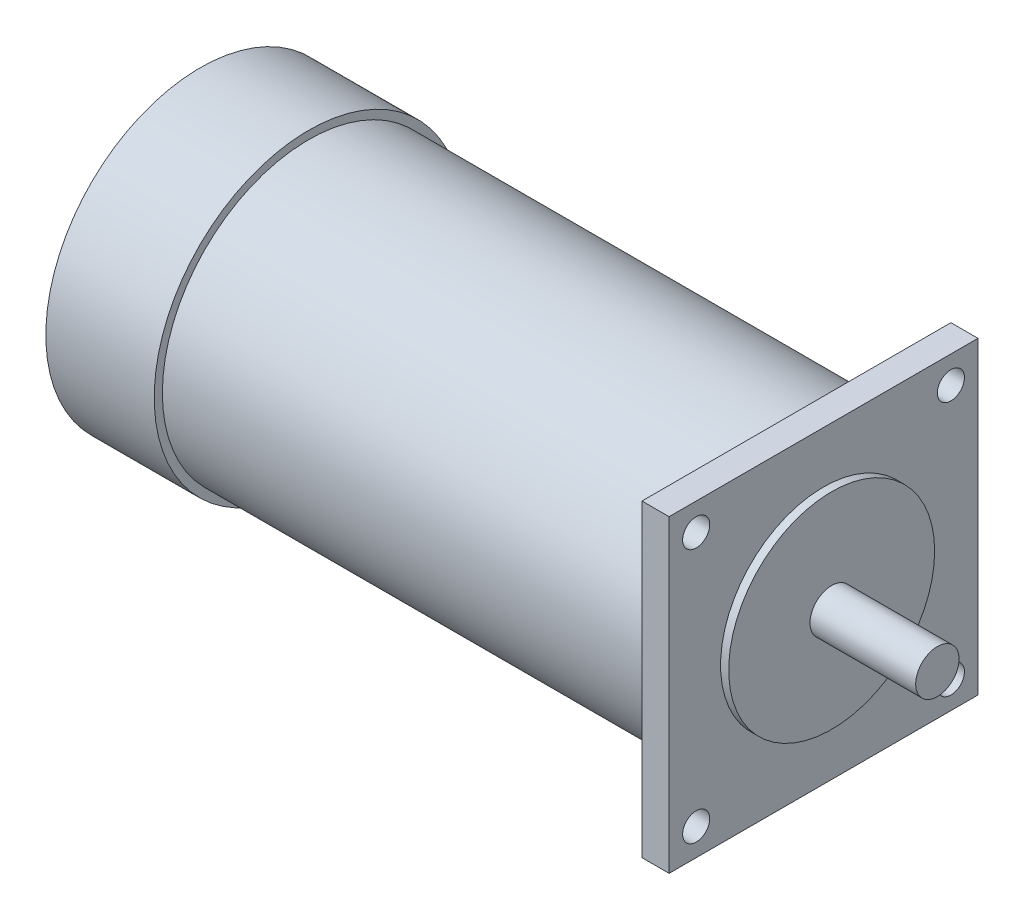
SolidWorks part; units mm, degrees
ref_plane "前视基准面" through (0, 0, 0) normal (0, 0, 1) x (1, 0, 0)
ref_plane "上视基准面" through (0, 0, 0) normal (0, 1, 0) x (1, 0, 0)
ref_plane "右视基准面" through (0, 0, 0) normal (1, 0, 0) x (0, 0, -1)
sketch "草图1" plane through (0, 0, 0) normal (1, 0, 0) x (0, 0, -1)
  line L1 (-28.5, -28.5) -> (28.5, -28.5)
  line L2 (-28.5, -28.5) -> (-28.5, 28.5)
  line L3 (-28.5, 28.5) -> (28.5, 28.5)
  line L4 (28.5, -28.5) -> (28.5, 28.5)
  line L5 (-28.5, -28.5) -> (28.5, 28.5) construction
  line L6 (-28.5, 28.5) -> (28.5, -28.5) construction
  circle A0 centre (0, 0) radius 19
  circle A1 centre (0, 0) radius 4
  point P0 (0, 0)
  dimension "D3" = 38
  dimension "D4" = 8
  dimension "D1" = 57
  dimension "D2" = 57
extrude "凸台-拉伸1" add sketch "草图1" along normal blind 21 contours A1 region at (0, 0, 0)
extrude "凸台-拉伸2" add sketch "草图1<3>" along normal blind 1.5 contours A0 A1 region at (0, 0, 18.4626)
sketch "草图1<3>" plane through (0, 0, 0) normal (1, 0, 0) x (0, 0, -1) same geometry as "草图1"
extrude "凸台-拉伸3" add sketch "草图1<4>" against normal blind 115 separate body contours L1 L4 L3 L2 A0 region at (0, 0, 27.6939)
sketch "草图1<4>" plane through (0, 0, 0) normal (1, 0, 0) x (0, 0, -1) same geometry as "草图1"
sketch "草图3" plane through (0, 0, 0) normal (1, 0, 0) x (0, 0, -1)
  line L4 (-28.5, -28.5) -> (28.5, -28.5)
  line L5 (28.5, -28.5) -> (28.5, 28.5)
  line L6 (28.5, 28.5) -> (-28.5, 28.5)
  line L7 (-28.5, 28.5) -> (-28.5, -28.5)
  line L8 (-28.5, -28.5) -> (28.5, -28.5)
  line L9 (28.5, -28.5) -> (28.5, 28.5)
  line L10 (28.5, 28.5) -> (-28.5, 28.5)
  line L11 (-28.5, 28.5) -> (-28.5, -28.5)
  line L16 (-28.5, 28.5) -> (0, 0) construction
  line L17 (0, 0) -> (28.5, -28.5) construction
  line L18 (-28.5, -28.5) -> (28.5, 28.5) construction
  circle A0 centre (-23.5, 23.5) radius 2.5
  circle A1 centre (23.5, 23.5) radius 2.5
  circle A2 centre (23.5, -23.5) radius 2.5
  circle A3 centre (-23.5, -23.5) radius 2.5
  point P17 (0, 0)
  dimension "D2" = 5
  dimension "D3" = 5
  dimension "D1" = 0
  dimension "D4" = 4
ref_plane "基准面2" through (21, 0, 0) normal (1, 0, 0) x (0, 0, -1)
sketch "草图5" plane through (21, 0, 0) normal (1, 0, 0) x (0, 0, -1)
  line L1 (-1.9365, 3.5) -> (1.9365, 3.5)
  circle A0 centre (0, 0) radius 4 construction
ref_plane "基准面3" through (0, 3.5, 0) normal (0, 1, 0) x (1, 0, 0)
sketch "草图6" plane through (0, 3.5, 0) normal (0, 1, 0) x (1, 0, 0)
  line L0 (21, -1.9365) -> (21, 1.9365) construction
  line L1 (21, -11.5764) -> (21, 11.5764) construction
  line L2 (21, -4) -> (6, -4)
  line L3 (21, -4) -> (21, 4)
  line L4 (21, 4) -> (6, 4)
  line L5 (6, -4) -> (6, 4)
  line L6 (1.5, -4) -> (21, -4) construction
  line L7 (21, 4) -> (1.5, 4) construction
  point P0 (21, 0)
  point P1 (21, 0)
  dimension "D1" = 15
ref_plane "基准面4" through (-115, 0, 0) normal (1, 0, 0) x (0, 0, -1)
sketch "草图9" plane through (-115, 0, 0) normal (1, 0, 0) x (0, 0, -1)
  circle A0 centre (0, 0) radius 28.5
  dimension "D1" = 57
extrude "切除-拉伸1" cut sketch "草图9" along normal blind 20 flip side to cut
sketch "草图10" plane through (-115, 0, 0) normal (1, 0, 0) x (0, 0, -1)
  circle A0 centre (0, 0) radius 27
  dimension "D1" = 54
ref_plane "基准面5" through (-95, 0, 0) normal (1, 0, 0) x (0, 0, -1)
sketch "草图11" plane through (-95, 0, 0) normal (1, 0, 0) x (0, 0, -1)
  circle A0 centre (0, 0) radius 27
extrude "切除-拉伸2" cut sketch "草图11" along normal blind 90 flip side to cut
ref_plane "基准面6" through (0, 0, 0) normal (1, 0, 0) x (0, 0, -1)
sketch "草图16" plane through (0, 0, 0) normal (1, 0, 0) x (0, 0, -1)
  circle A0 centre (-23.5, 23.5) radius 2.5
  circle A1 centre (23.5, 23.5) radius 2.5
  circle A2 centre (23.5, -23.5) radius 2.5
  circle A3 centre (-23.5, -23.5) radius 2.5
  point P12 (0, 0)
  dimension "D1" = 5
  dimension "D2" = 4
extrude "切除-拉伸3" cut sketch "草图16" against normal blind 5
